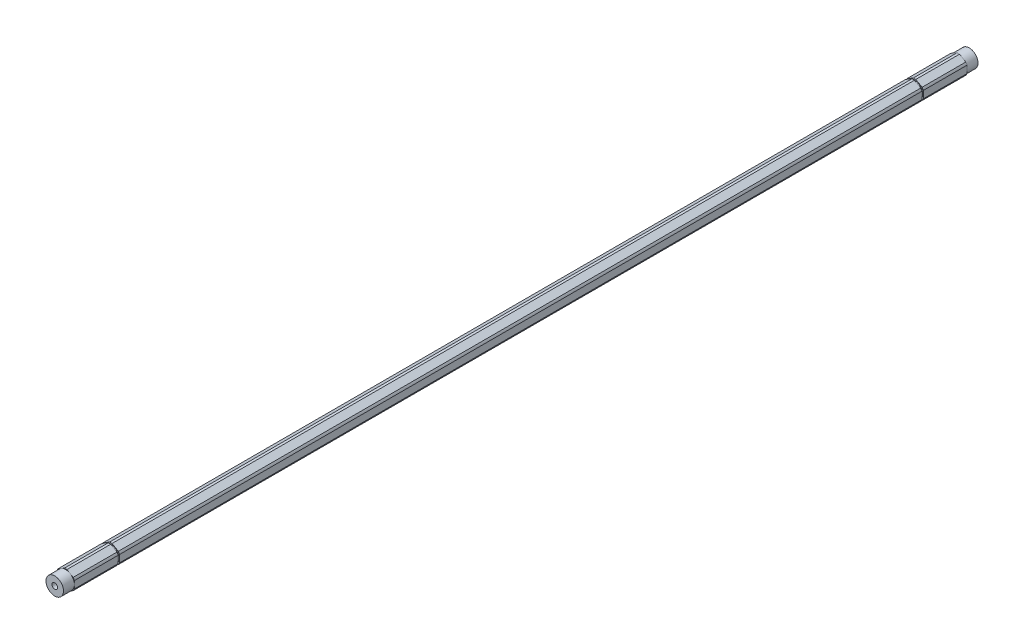
SolidWorks part; units mm, degrees
material "7075-T6 (SN)"
ref_plane "Front Plane" through (0, 0, 0) normal (0, 0, 1) x (1, 0, 0)
ref_plane "Top Plane" through (0, 0, 0) normal (0, 1, 0) x (1, 0, 0)
ref_plane "Right Plane" through (0, 0, 0) normal (1, 0, 0) x (0, 0, -1)
sketch "Sketch1" plane through (0, 0, 0) normal (0, 0, 1) x (1, 0, 0)
  line L1 (0, 7.3323) -> (-6.35, 3.6662)
  line L2 (-6.35, 3.6662) -> (-6.35, -3.6662)
  line L3 (-6.35, -3.6662) -> (0, -7.3323)
  line L4 (0, -7.3323) -> (6.35, -3.6662)
  line L5 (6.35, -3.6662) -> (6.35, 3.6662)
  line L6 (6.35, 3.6662) -> (0, 7.3323)
  circle A0 centre (0, 0) radius 6.35 construction
  circle A1 centre (0, 0) radius 2.0193
  circle A2 centre (0, 0) radius 6.875
  dimension "D1" = 12.7
  dimension "D2" = 4.0386
  dimension "D3" = 13.75
extrude "Boss-Extrude1" add sketch "Sketch1" along normal mid plane 663.575 contours L5 A2 L6 L1 L2 L3 L4 A1 region at (0, 6.6878, 0)
sketch "Sketch2" plane through (0, 0, -331.7875) normal (0, 0, -1) x (-1, 0, 0)
  circle A0 centre (0, 0) radius 6.35
  dimension "D1" = 12.7
extrude "Cut-Extrude-Thin1" cut sketch "Sketch2" against normal blind 7.9375 thin thin type one direction wall 2.54
sketch "Sketch3" plane through (0, 0, 0) normal (0, 1, 0) x (1, 0, 0)
  line L1 (8.6172, 292.1) -> (5.9436, 292.1)
  line L2 (8.6172, 292.1) -> (8.6172, 291.1094)
  line L3 (8.6172, 291.1094) -> (5.9436, 291.1094)
  line L4 (5.9436, 292.1) -> (5.9436, 291.1094)
  line L9 (6.35, 331.7875) -> (-6.35, 331.7875) construction
  line L11 (0, -331.7875) -> (0, 323.85) construction
  dimension "D1" = 0.9906
  dimension "D2" = 39.6875
  dimension "D3" = 5.9436
revolve "Cut-Revolve4" cut sketch "Sketch3" angle 360 about axis through (0, 0, -323.85) along (0, 0, -1)
mirror "Mirror1" about plane through (0, 0, 0) normal (0, 0, 1) of "Cut-Revolve4", "Cut-Extrude-Thin1"
hole_wizard "#10-32 Tapped Hole1" positions "3DSketch1" profile "Sketch4" tap size "#10-32" standard "ANSI Inch"
sketch3d "3DSketch1"
  circle A0 centre (0, 0, 331.7875) radius 2.0193 construction
  circle A1 centre (0, 0, -331.7875) radius 2.0193 construction
  point P0 (0, 0, -331.7875)
  point P2 (0, 0, 331.7875)
  point P8 (0, 0, 333.8068)
  point P12 (0, 0, -329.7682)
sketch "Sketch4" plane through (0, 0, -331.7875) normal (1, 0, 0) x (0, 1, 0)
  line L0 (0, 0) -> (0, 13.2428)
  line L1 (0, 13.2428) -> (2.0193, 12.0294)
  line L2 (2.0193, 12.0294) -> (2.0193, 0)
  line L5 (2.0193, 0) -> (0, 0)
  line L10 (0, 13.2428) -> (-2.0193, 12.0294) construction
  line L11 (0, -6.35) -> (0, 107.95) construction
  dimension "Tap Drill Dia." = 4.0386
  dimension "Tap Drill Depth" = 12.0294
  dimension "Drill Angle" = 118
cosmetic thread "Hole Thread1" parameters "D1"=9.652, "D2"=4.826
cosmetic thread "Hole Thread2" parameters "D1"=9.652, "D2"=4.826
equation "\"D3@Sketch1\"=13.75mm"
